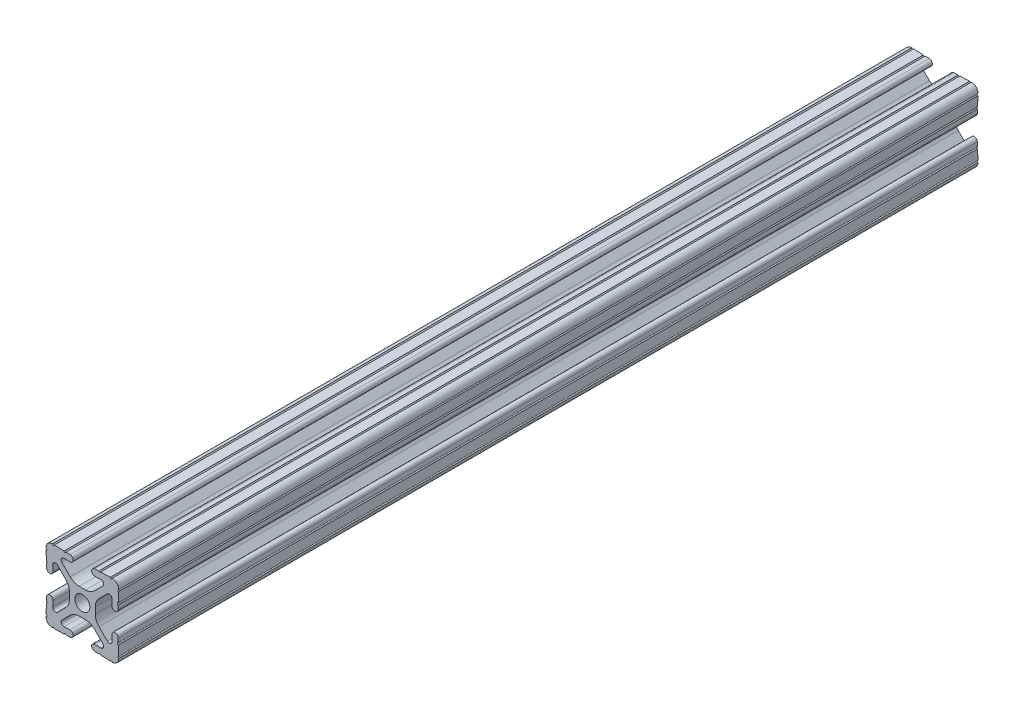
SolidWorks part; units mm, degrees
material "6063-T5"
ref_plane "Front Plane" through (0, 0, 0) normal (0, 0, 1) x (1, 0, 0)
ref_plane "Top Plane" through (0, 0, 0) normal (0, 1, 0) x (1, 0, 0)
ref_plane "Right Plane" through (0, 0, 0) normal (1, 0, 0) x (0, 0, -1)
sketch "Sketch1" plane through (0, 0, 0) normal (0, 0, 1) x (1, 0, 0)
  line L0 (0, 12.7) -> (-12.7814, 12.7) construction
  line L1 (-4.5085, 0) -> (-4.5085, 2.9459)
  line L2 (-6.0437, 12.5461) -> (-10.0976, 12.6876) construction
  line L3 (-11.5616, 12.4229) -> (-4.3159, 12.1699) construction
  line L4 (-6.4364, 10.3486) -> (-6.3592, 12.5571) construction
  line L6 (-2.9459, 4.5085) -> (0, 4.5085)
  line L7 (0, 0) -> (0, 12.7) construction
  line L8 (0, 0) -> (-12.7814, 0) construction
  line L9 (0.7813, 0.7813) -> (-0.7813, -0.7813) construction
  line L10 (-2.9459, 4.5085) -> (-7.1484, 8.711)
  line L11 (-4.5085, 2.9459) -> (-8.711, 7.1484)
  line L13 (0, 0) -> (-12.7814, 12.7814) construction
  line L14 (-10.4131, 12.6987) -> (-4.3048, 12.4853)
  line L15 (-4.3048, 12.4853) -> (-4.382, 10.2769) construction
  line L16 (-4.382, 10.2769) -> (-6.4364, 10.3486)
  line L17 (-12.6987, 10.4131) -> (-12.4853, 4.3048)
  line L18 (-10.2769, 4.382) -> (-10.3486, 6.4364)
  circle A0 centre (0, 0) radius 2.6035
  arc A1 (-4.382, 10.2769) -> (-4.3048, 12.4853) centre (-4.3434, 11.3811) ccw
  arc A2 (-7.1484, 8.711) -> (-6.4364, 10.3486) centre (-6.4698, 9.3896) cw
  arc A3 (-8.711, 7.1484) -> (-10.3486, 6.4364) centre (-9.3896, 6.4698) ccw
  arc A4 (-10.2769, 4.382) -> (-12.4853, 4.3048) centre (-11.3811, 4.3434) cw
  arc A5 (-10.4131, 12.6987) -> (-12.6987, 10.4131) centre (-10.4902, 10.4902) ccw
  arc A6 (-10.4131, 12.6987) -> (-9.7821, 12.6766) centre (-10.0976, 12.6876) ccw
  arc A7 (-6.3592, 12.5571) -> (-5.7282, 12.5351) centre (-6.0437, 12.5461) ccw
  arc A8 (-12.5571, 6.3592) -> (-12.5351, 5.7282) centre (-12.5461, 6.0437) cw
  arc A9 (-12.6987, 10.4131) -> (-12.6766, 9.7821) centre (-12.6876, 10.0976) cw
  dimension "D1" = 5.207
  dimension "D5" = 14.859
  dimension "D9" = 2
  dimension "D2" = 25.4
  dimension "D12" = 0.6314
  dimension "D10" = 2.2098
  dimension "D3" = 9.017
  dimension "D4" = 9.017
  dimension "D6" = 25.4
  dimension "D7" = 6.477
  dimension "D8" = 2.2098
  dimension "D11" = 12.7
sketch "Sketch3" plane through (0, 0, 0) normal (0, 0, 1) x (1, 0, 0)
  line L0 (-2.9459, 4.5085) -> (0, 4.5085) construction
  line L1 (-2.9459, 4.5085) -> (-7.1484, 8.711) construction
  line L2 (-4.382, 10.2769) -> (-6.4364, 10.3486) construction
  line L3 (-10.4131, 12.6987) -> (-4.3048, 12.4853) construction
  line L4 (-4.5085, 0) -> (-4.5085, 2.9459) construction
  line L5 (-4.5085, 2.9459) -> (-8.711, 7.1484) construction
  line L6 (-10.2769, 4.382) -> (-10.3486, 6.4364) construction
  line L7 (-12.6987, 10.4131) -> (-12.4853, 4.3048) construction
  line L8 (-1.1153, 4.5085) -> (1.1153, 4.5085)
  line L9 (-4.2404, 5.803) -> (-7.1484, 8.711)
  line L10 (-4.382, 10.2769) -> (-6.4364, 10.3486)
  line L11 (-9.7821, 12.6766) -> (-6.3592, 12.5571)
  line L12 (-4.5085, -1.1153) -> (-4.5085, 1.1153)
  line L13 (-5.803, 4.2404) -> (-8.711, 7.1484)
  line L14 (-10.2769, 4.382) -> (-10.3486, 6.4364)
  line L15 (-12.6766, 9.7821) -> (-12.5571, 6.3592)
  line L16 (-5.7282, 12.5351) -> (-4.3048, 12.4853)
  line L17 (-12.5351, 5.7282) -> (-12.4853, 4.3048)
  line L18 (0, 0) -> (0, 12.7) construction
  line L19 (0, 0) -> (-12.7814, 0) construction
  line L20 (12.5351, 5.7282) -> (12.4853, 4.3048)
  line L21 (5.7282, 12.5351) -> (4.3048, 12.4853)
  line L22 (12.6766, 9.7821) -> (12.5571, 6.3592)
  line L23 (10.2769, 4.382) -> (10.3486, 6.4364)
  line L24 (5.803, 4.2404) -> (8.711, 7.1484)
  line L25 (4.5085, -1.1153) -> (4.5085, 1.1153)
  line L26 (9.7821, 12.6766) -> (6.3592, 12.5571)
  line L27 (4.382, 10.2769) -> (6.4364, 10.3486)
  line L28 (4.2404, 5.803) -> (7.1484, 8.711)
  line L29 (4.2404, -5.803) -> (7.1484, -8.711)
  line L30 (4.382, -10.2769) -> (6.4364, -10.3486)
  line L31 (9.7821, -12.6766) -> (6.3592, -12.5571)
  line L32 (5.803, -4.2404) -> (8.711, -7.1484)
  line L33 (10.2769, -4.382) -> (10.3486, -6.4364)
  line L34 (12.6766, -9.7821) -> (12.5571, -6.3592)
  line L35 (5.7282, -12.5351) -> (4.3048, -12.4853)
  line L36 (12.5351, -5.7282) -> (12.4853, -4.3048)
  line L37 (-12.5351, -5.7282) -> (-12.4853, -4.3048)
  line L38 (-5.7282, -12.5351) -> (-4.3048, -12.4853)
  line L39 (-12.6766, -9.7821) -> (-12.5571, -6.3592)
  line L40 (-10.2769, -4.382) -> (-10.3486, -6.4364)
  line L41 (-5.803, -4.2404) -> (-8.711, -7.1484)
  line L42 (-9.7821, -12.6766) -> (-6.3592, -12.5571)
  line L43 (-4.382, -10.2769) -> (-6.4364, -10.3486)
  line L44 (-4.2404, -5.803) -> (-7.1484, -8.711)
  line L45 (-1.1153, -4.5085) -> (1.1153, -4.5085)
  arc A0 (-10.4131, 12.6987) -> (-9.7821, 12.6766) centre (-10.0976, 12.6876) ccw construction
  arc A1 (-6.4364, 10.3486) -> (-7.1484, 8.711) centre (-6.4698, 9.3896) ccw construction
  arc A2 (-4.382, 10.2769) -> (-4.3048, 12.4853) centre (-4.3434, 11.3811) ccw construction
  arc A3 (-8.711, 7.1484) -> (-10.3486, 6.4364) centre (-9.3896, 6.4698) ccw construction
  arc A4 (-12.4853, 4.3048) -> (-10.2769, 4.382) centre (-11.3811, 4.3434) ccw construction
  arc A5 (-6.3592, 12.5571) -> (-5.7282, 12.5351) centre (-6.0437, 12.5461) ccw construction
  arc A6 (-10.4131, 12.6987) -> (-12.6987, 10.4131) centre (-10.4902, 10.4902) ccw construction
  arc A7 (-12.6766, 9.7821) -> (-12.6987, 10.4131) centre (-12.6876, 10.0976) ccw construction
  arc A8 (-12.5351, 5.7282) -> (-12.5571, 6.3592) centre (-12.5461, 6.0437) ccw construction
  arc A9 (-10.4131, 12.6987) -> (-9.7821, 12.6766) centre (-10.0976, 12.6876) ccw
  arc A10 (-6.4364, 10.3486) -> (-7.1484, 8.711) centre (-6.4698, 9.3896) ccw
  arc A11 (-4.382, 10.2769) -> (-4.3048, 12.4853) centre (-4.3434, 11.3811) ccw
  arc A12 (-8.711, 7.1484) -> (-10.3486, 6.4364) centre (-9.3896, 6.4698) ccw
  arc A13 (-12.4853, 4.3048) -> (-10.2769, 4.382) centre (-11.3811, 4.3434) ccw
  arc A14 (-6.3592, 12.5571) -> (-5.7282, 12.5351) centre (-6.0437, 12.5461) ccw
  arc A15 (-10.4131, 12.6987) -> (-12.6987, 10.4131) centre (-10.4902, 10.4902) ccw
  arc A16 (-12.6766, 9.7821) -> (-12.6987, 10.4131) centre (-12.6876, 10.0976) ccw
  arc A17 (-12.5351, 5.7282) -> (-12.5571, 6.3592) centre (-12.5461, 6.0437) ccw
  arc A18 (-1.1153, 4.5085) -> (-4.2404, 5.803) centre (-1.1153, 8.9281) cw
  arc A19 (4.5085, 1.1153) -> (5.803, 4.2404) centre (8.9281, 1.1153) cw
  arc A20 (1.1153, 4.5085) -> (4.2404, 5.803) centre (1.1153, 8.9281) ccw
  arc A21 (-4.5085, 1.1153) -> (-5.803, 4.2404) centre (-8.9281, 1.1153) ccw
  arc A22 (12.5351, 5.7282) -> (12.5571, 6.3592) centre (12.5461, 6.0437) cw
  arc A23 (12.6766, 9.7821) -> (12.6987, 10.4131) centre (12.6876, 10.0976) cw
  arc A24 (10.4131, 12.6987) -> (12.6987, 10.4131) centre (10.4902, 10.4902) cw
  arc A25 (6.3592, 12.5571) -> (5.7282, 12.5351) centre (6.0437, 12.5461) cw
  arc A26 (12.4853, 4.3048) -> (10.2769, 4.382) centre (11.3811, 4.3434) cw
  arc A27 (8.711, 7.1484) -> (10.3486, 6.4364) centre (9.3896, 6.4698) cw
  arc A28 (4.382, 10.2769) -> (4.3048, 12.4853) centre (4.3434, 11.3811) cw
  arc A29 (6.4364, 10.3486) -> (7.1484, 8.711) centre (6.4698, 9.3896) cw
  arc A30 (10.4131, 12.6987) -> (9.7821, 12.6766) centre (10.0976, 12.6876) cw
  arc A31 (10.4131, -12.6987) -> (9.7821, -12.6766) centre (10.0976, -12.6876) ccw
  arc A32 (6.4364, -10.3486) -> (7.1484, -8.711) centre (6.4698, -9.3896) ccw
  arc A33 (4.382, -10.2769) -> (4.3048, -12.4853) centre (4.3434, -11.3811) ccw
  arc A34 (8.711, -7.1484) -> (10.3486, -6.4364) centre (9.3896, -6.4698) ccw
  arc A35 (12.4853, -4.3048) -> (10.2769, -4.382) centre (11.3811, -4.3434) ccw
  arc A36 (6.3592, -12.5571) -> (5.7282, -12.5351) centre (6.0437, -12.5461) ccw
  arc A37 (10.4131, -12.6987) -> (12.6987, -10.4131) centre (10.4902, -10.4902) ccw
  arc A38 (12.6766, -9.7821) -> (12.6987, -10.4131) centre (12.6876, -10.0976) ccw
  arc A39 (12.5351, -5.7282) -> (12.5571, -6.3592) centre (12.5461, -6.0437) ccw
  arc A40 (-4.5085, -1.1153) -> (-5.803, -4.2404) centre (-8.9281, -1.1153) cw
  arc A41 (1.1153, -4.5085) -> (4.2404, -5.803) centre (1.1153, -8.9281) cw
  arc A42 (4.5085, -1.1153) -> (5.803, -4.2404) centre (8.9281, -1.1153) ccw
  arc A43 (-1.1153, -4.5085) -> (-4.2404, -5.803) centre (-1.1153, -8.9281) ccw
  arc A44 (-12.5351, -5.7282) -> (-12.5571, -6.3592) centre (-12.5461, -6.0437) cw
  arc A45 (-12.6766, -9.7821) -> (-12.6987, -10.4131) centre (-12.6876, -10.0976) cw
  arc A46 (-10.4131, -12.6987) -> (-12.6987, -10.4131) centre (-10.4902, -10.4902) cw
  arc A47 (-6.3592, -12.5571) -> (-5.7282, -12.5351) centre (-6.0437, -12.5461) cw
  arc A48 (-12.4853, -4.3048) -> (-10.2769, -4.382) centre (-11.3811, -4.3434) cw
  arc A49 (-8.711, -7.1484) -> (-10.3486, -6.4364) centre (-9.3896, -6.4698) cw
  arc A50 (-4.382, -10.2769) -> (-4.3048, -12.4853) centre (-4.3434, -11.3811) cw
  arc A51 (-6.4364, -10.3486) -> (-7.1484, -8.711) centre (-6.4698, -9.3896) cw
  arc A52 (-10.4131, -12.6987) -> (-9.7821, -12.6766) centre (-10.0976, -12.6876) cw
  circle A53 centre (0, 0) radius 2.6035 construction
  circle A54 centre (0, 0) radius 2.6035
  point P135 (4.5085, 0)
  dimension "D2" = 4.4196
extrude "Extrude1" add sketch "Sketch3" along normal mid plane 1219.2
sketch "Sketch4" plane through (-12.32, -0.4302, 0) normal (-0.9994, -0.0349, 0) x (0, 0, 1)
  line L1 (-609.6, 28.9362) -> (309.6, 28.9362)
  line L2 (-609.6, 28.9362) -> (-609.6, -29.0805)
  line L3 (-609.6, -29.0805) -> (309.6, -29.0805)
  line L4 (309.6, 28.9362) -> (309.6, -29.0805)
  dimension "D1" = 919.2
extrude "Cut-Extrude1" cut sketch "Sketch4" against normal blind 64 and the other way blind 64
equation "\"D10@Sketch1\" = \"D8@Sketch1\""
equation "\"D11@Sketch1\" = \"D6@Sketch1\"/2"
equation "\"D12@Sketch1\" = \"D8@Sketch1\"/3.5"
equation "\"D2@Sketch3\" = \"D8@Sketch1\"*2"
